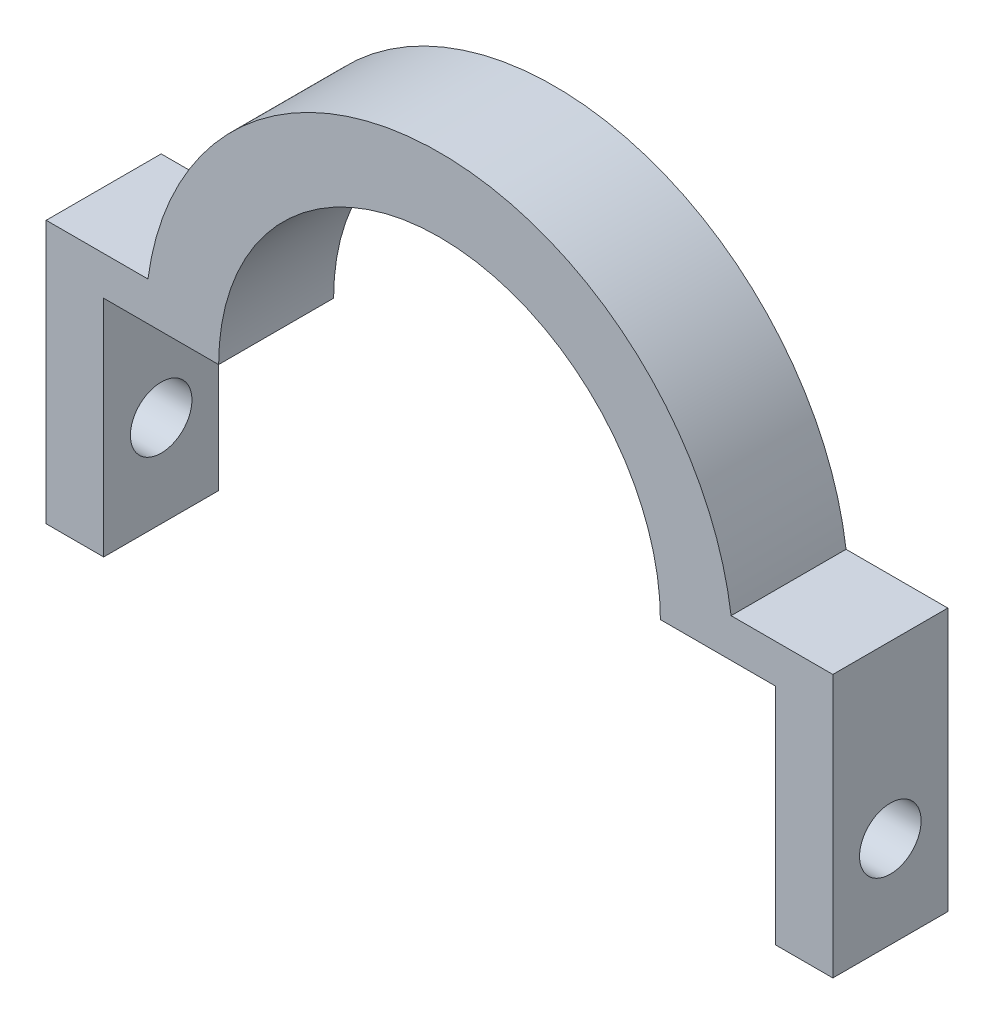
SolidWorks part; units mm, degrees
ref_plane "Front Plane" through (0, 0, 0) normal (0, 0, 1) x (1, 0, 0)
ref_plane "Top Plane" through (0, 0, 0) normal (0, 1, 0) x (1, 0, 0)
ref_plane "Right Plane" through (0, 0, 0) normal (1, 0, 0) x (0, 0, -1)
sketch "Sketch1" plane through (0, 0, 0) normal (0, 0, 1) x (1, 0, 0)
  line L10 (39.412, 14.521) -> (45.032, 14.521)
  line L17 (41.857, 12.38) -> (41.857, 0)
  line L18 (41.857, 0) -> (45.032, 0)
  line L25 (35.507, 12.38) -> (41.857, 12.38)
  line L26 (45.032, 14.521) -> (45.032, 0)
  line L27 (11.107, 12.38) -> (4.757, 12.38)
  line L28 (7.2019, 14.521) -> (1.582, 14.521)
  line L29 (1.582, 14.521) -> (1.582, 0)
  line L30 (4.757, 12.38) -> (4.757, 0)
  line L31 (4.757, 0) -> (1.582, 0)
  arc A0 (35.507, 12.38) -> (11.107, 12.38) centre (23.307, 12.38) ccw
  arc A1 (7.2019, 14.521) -> (39.412, 14.521) centre (23.307, 12.38) cw
  dimension "D1" = 24.4
  dimension "D8" = 16.2467
  dimension "D2" = 6.35
  dimension "D3" = 6.35
  dimension "D4" = 3.175
  dimension "D5" = 3.175
  dimension "D6" = 12.38
  dimension "D7" = 12.38
extrude "Boss-Extrude1" add sketch "Sketch1" along normal blind 6.35
sketch "Sketch2" plane through (45.032, 0, 0) normal (1, 0, 0) x (0, 0, -1)
  line L1 (-6.35, 0) -> (0, 0) construction
  circle A1 centre (-3.175, 5.08) radius 1.7
  point P2 (0, 0)
  point P5 (-3.175, 0)
  point P8 (-1.8655, 0)
  dimension "D1" = 3.4
  dimension "D3" = 5.08
  dimension "D2" = 0
extrude "Cut-Extrude1" cut sketch "Sketch2" against normal through all and the other way through all
